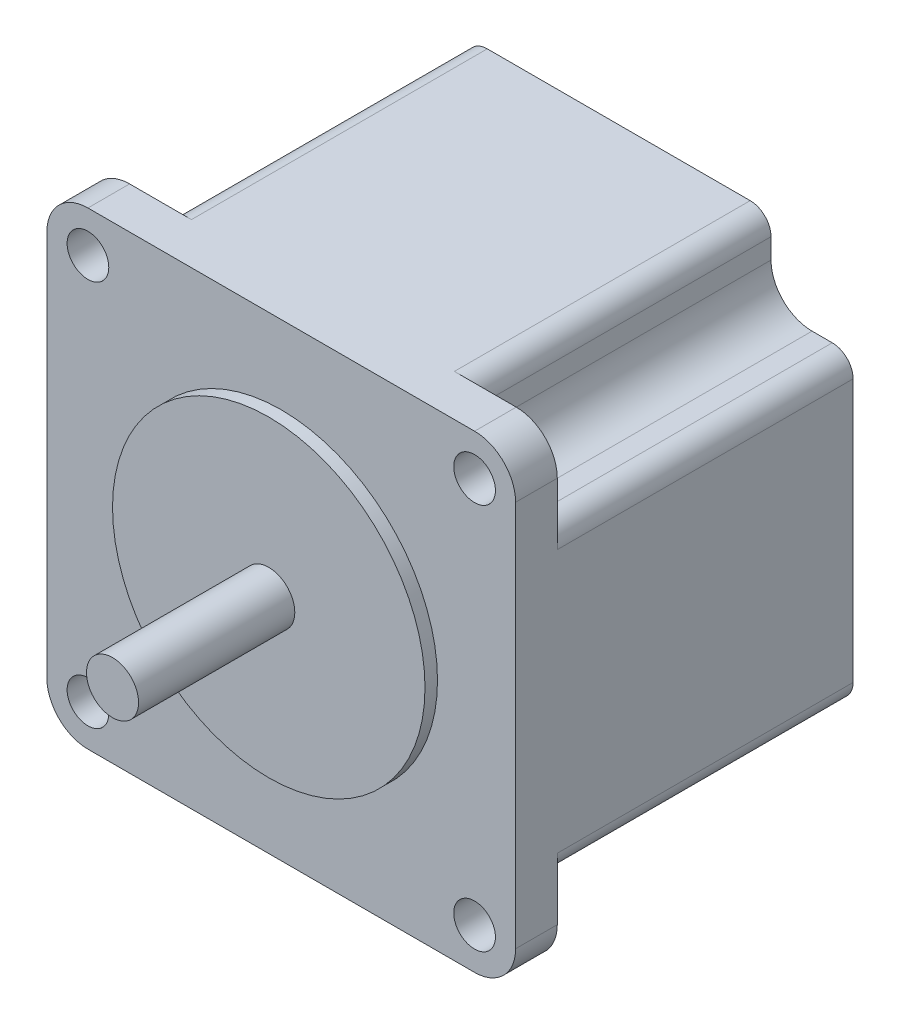
SolidWorks part; units mm, degrees
ref_plane "Front Plane" through (0, 0, 0) normal (0, 0, 1) x (1, 0, 0)
ref_plane "Top Plane" through (0, 0, 0) normal (0, 1, 0) x (1, 0, 0)
ref_plane "Right Plane" through (0, 0, 0) normal (1, 0, 0) x (0, 0, -1)
sketch "Sketch1" plane through (0, 0, 0) normal (0, 0, 1) x (1, 0, 0)
  line L1 (-23.5712, 28.575) -> (23.5712, 28.575)
  line L2 (-28.575, 23.5712) -> (-28.575, -23.5712)
  line L3 (-23.5712, -28.575) -> (23.5712, -28.575)
  line L4 (28.575, 23.5712) -> (28.575, -23.5712)
  line L5 (-28.575, 28.575) -> (28.575, -28.575) construction
  line L6 (-28.575, -28.575) -> (28.575, 28.575) construction
  circle A0 centre (-23.5712, 23.5712) radius 2.54
  circle A1 centre (23.5712, 23.5712) radius 2.54
  circle A2 centre (23.5712, -23.5712) radius 2.54
  circle A3 centre (-23.5712, -23.5712) radius 2.54
  arc A4 (-23.5712, 28.575) -> (-28.575, 23.5712) centre (-23.5712, 23.5712) ccw
  arc A5 (28.575, 23.5712) -> (23.5712, 28.575) centre (23.5712, 23.5712) ccw
  arc A6 (23.5712, -28.575) -> (28.575, -23.5712) centre (23.5712, -23.5712) ccw
  arc A7 (-28.575, -23.5712) -> (-23.5712, -28.575) centre (-23.5712, -23.5712) ccw
  point P0 (0, 0)
  dimension "D5" = 5.08
  dimension "D6" = 5.08
  dimension "D7" = 5.08
  dimension "D8" = 5.08
  dimension "D9" = 5.0038
  dimension "D1" = 57.15
  dimension "D2" = 57.15
  dimension "D3" = 47.1424
  dimension "D4" = 47.1424
extrude "Extrude1" add sketch "Sketch1" against normal mid plane 41.148
sketch "Sketch2" plane through (0, 0, 20.574) normal (0, 0, 1) x (1, 0, 0)
  circle A0 centre (0, 0) radius 19.05
  dimension "D1" = 38.1
extrude "Extrude2" add sketch "Sketch2" along normal blind 1.524
sketch "Sketch3" plane through (0, 0, 20.574) normal (0, 0, 1) x (1, 0, 0)
  circle A0 centre (0, 0) radius 3.175
  dimension "D1" = 6.35
extrude "Extrude3" add sketch "Sketch3" along normal blind 20.574
sketch "Sketch4" plane through (0, 0, -20.574) normal (0, 0, -1) x (-1, 0, 0)
  line L0 (-23.5712, 18.5674) -> (-28.575, 18.5674)
  line L1 (-28.575, -23.5712) -> (-28.575, 23.5712) construction
  line L2 (-28.575, 18.5674) -> (-28.575, 23.5712)
  line L3 (-18.5674, 23.5712) -> (-18.5674, 28.575)
  line L4 (-23.5712, 28.575) -> (23.5712, 28.575) construction
  line L5 (-18.5674, 28.575) -> (-23.5712, 28.575)
  line L6 (23.5712, 18.5674) -> (28.575, 18.5674)
  line L7 (28.575, 23.5712) -> (28.575, -23.5712) construction
  line L8 (28.575, 18.5674) -> (28.575, 23.5712)
  line L9 (18.5674, 23.5712) -> (18.5674, 28.575)
  line L10 (18.5674, 28.575) -> (23.5712, 28.575)
  line L11 (23.5712, -18.5674) -> (28.575, -18.5674)
  line L12 (28.575, -18.5674) -> (28.575, -23.5712)
  line L13 (18.5674, -23.5712) -> (18.5674, -28.575)
  line L14 (23.5712, -28.575) -> (-23.5712, -28.575) construction
  line L15 (18.5674, -28.575) -> (23.5712, -28.575)
  line L16 (-18.5674, -23.5712) -> (-18.5674, -28.575)
  line L17 (-18.5674, -28.575) -> (-23.5712, -28.575)
  line L18 (-23.5712, -18.5674) -> (-28.575, -18.5674)
  line L19 (-28.575, -18.5674) -> (-28.575, -23.5712)
  arc A0 (-23.5712, 18.5674) -> (-18.5674, 23.5712) centre (-23.5712, 23.5712) ccw
  arc A1 (-28.575, -23.5712) -> (-23.5712, -28.575) centre (-23.5712, -23.5712) ccw
  arc A2 (23.5712, -18.5674) -> (18.5674, -23.5712) centre (23.5712, -23.5712) ccw
  arc A3 (18.5674, 23.5712) -> (23.5712, 18.5674) centre (23.5712, 23.5712) ccw
  arc A4 (-23.5712, 28.575) -> (-28.575, 23.5712) centre (-23.5712, 23.5712) ccw
  arc A5 (28.575, 23.5712) -> (23.5712, 28.575) centre (23.5712, 23.5712) ccw
  arc A6 (23.5712, -28.575) -> (28.575, -23.5712) centre (23.5712, -23.5712) ccw
  arc A7 (-18.5674, -23.5712) -> (-23.5712, -18.5674) centre (-23.5712, -23.5712) ccw
extrude "Extrude4" cut sketch "Sketch4" against normal offset from surface (36.068 mm away) 5.08 up to face at (0, 0, 20.574)
fillet "Fillet1" radius 2.54 8 edges at (28.575, -18.5674, -2.54) (18.5674, -28.575, -2.54) (-18.5674, -28.575, -2.54) (-28.575, -18.5674, -2.54) (-28.575, 18.5674, -2.54) (-18.5674, 28.575, -2.54) (18.5674, 28.575, -2.54) (28.575, 18.5674, -2.54)
sketch "Sketch5" plane through (0, 0, -20.574) normal (0, 0, -1) x (-1, 0, 0)
  circle A0 centre (0, 0) radius 3.175
  dimension "D1" = 6.35
extrude "Extrude5" add sketch "Sketch5" along normal blind 14.986
sketch "Sketch6" plane through (0, 0, -20.574) normal (0, 0, -1) x (-1, 0, 0)
  line L0 (-16.0274, 28.575) -> (16.0274, 28.575) construction
  circle A0 centre (-23.0124, 0) radius 1.0782
  circle A1 centre (23.0124, 0) radius 1.0782
  dimension "D1" = 2.1565
  dimension "D2" = 2.1565
  dimension "D3" = 46.0248
  dimension "D4" = 23.0124
  dimension "D5" = 28.575
extrude "Extrude6" cut sketch "Sketch6" against normal blind 3.81
sketch "Sketch7" plane through (0, 0, 22.098) normal (0, 0, 1) x (1, 0, 0)
  circle A0 centre (0, 0) radius 6
  dimension "D1" = 12
ref_axis "shaft" through (0, 0, 22.098) along (0, 0, 1)
sketch "Sketch9" plane through (0, -28.575, 0) normal (0, -1, 0) x (1, 0, 0)
  line L0 (-16.0274, -20.574) -> (16.0274, -20.574) construction
  line L1 (12.8052, -20.574) -> (-14.3543, -20.574)
  line L2 (12.8052, -20.574) -> (12.8052, -38.6681)
  line L3 (12.8052, -38.6681) -> (-14.3543, -38.6681)
  line L4 (-14.3543, -20.574) -> (-14.3543, -38.6681)
extrude "Cut-Extrude1" cut sketch "Sketch9" against normal blind 56.642
